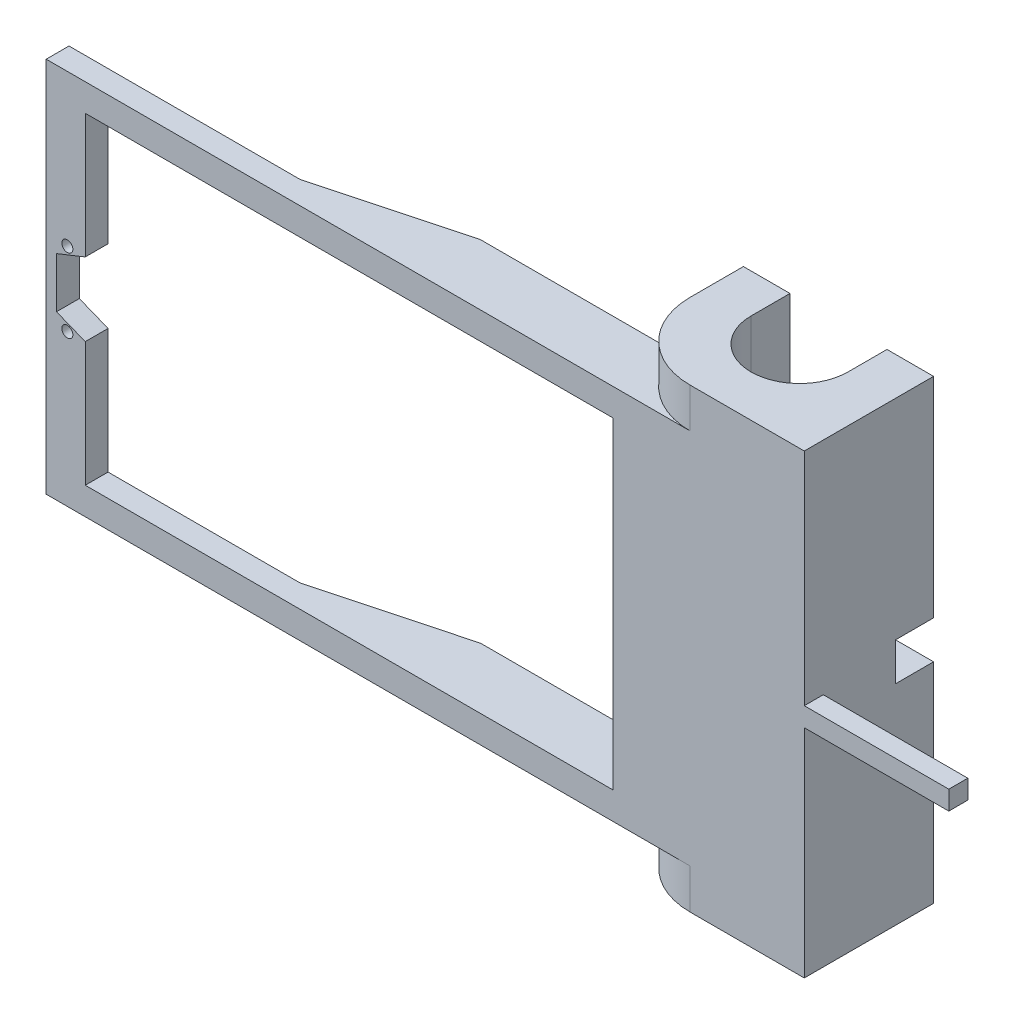
SolidWorks part; units mm, degrees
ref_plane "Front Plane" through (0, 0, 0) normal (0, 0, 1) x (1, 0, 0)
ref_plane "Top Plane" through (0, 0, 0) normal (0, 1, 0) x (1, 0, 0)
ref_plane "Right Plane" through (0, 0, 0) normal (1, 0, 0) x (0, 0, -1)
sketch "Sketch1" plane through (0, 0, 0) normal (0, 1, 0) x (1, 0, 0)
  line L1 (0, 0) -> (50, 0)
  line L2 (0, 0) -> (0, 34)
  line L3 (0, 34) -> (50, 34)
  line L4 (50, 0) -> (50, 34)
  dimension "D1" = 50
  dimension "D2" = 34
extrude "Boss-Extrude1" add sketch "Sketch1" along normal blind 120
sketch "Sketch2" plane through (0, 120, 0) normal (0, 1, 0) x (1, 0, 0)
  line L0 (0, 11) -> (50, 11) construction
  line L1 (0, 34) -> (0, 0) construction
  line L2 (50, 0) -> (50, 34) construction
  line L3 (25, 34) -> (25, 0) construction
  line L4 (50, 34) -> (0, 34) construction
  line L5 (0, 0) -> (50, 0) construction
  line L6 (12.25, 23.75) -> (12.25, 34)
  line L7 (12.25, 34) -> (37.75, 34)
  line L8 (37.75, 34) -> (37.75, 23.75)
  arc A0 (12.25, 23.75) -> (37.75, 23.75) centre (25, 23.75) ccw
  dimension "D1" = 23
extrude "Cut-Extrude2" cut sketch "Sketch2" against normal blind 120
fillet "Fillet1" radius 20 2 edges at (50, 60, 0) (0, 60, 0)
sketch "Sketch3" plane through (0, 0, -34) normal (0, 0, -1) x (-1, 0, 0)
  line L0 (0, 120) -> (0, 0) construction
  line L1 (0, 102) -> (-9.75, 102)
  line L2 (0, 102) -> (0, 18)
  line L3 (0, 18) -> (-9.75, 18)
  line L4 (-9.75, 102) -> (-9.75, 18)
  line L5 (-12.25, 120) -> (0, 120) construction
  line L6 (-12.25, 0) -> (-12.25, 120) construction
  line L7 (-12.25, 0) -> (0, 0) construction
  dimension "D1" = 18
  dimension "D2" = 2.5
  dimension "D3" = 18
extrude "Cut-Extrude3" cut sketch "Sketch3" against normal blind 31
sketch "Sketch4" plane through (0, 0, -34) normal (0, 0, -1) x (-1, 0, 0)
  line L0 (-37.75, 0) -> (-37.75, 120) construction
  line L1 (-37.75, 65) -> (-50, 65)
  line L2 (-37.75, 65) -> (-37.75, 55)
  line L3 (-37.75, 55) -> (-50, 55)
  line L4 (-50, 65) -> (-50, 55)
  line L5 (-50, 120) -> (-50, 0) construction
  line L6 (-50, 0) -> (-37.75, 0) construction
  dimension "D1" = 10
  dimension "D2" = 55
extrude "Cut-Extrude4" cut sketch "Sketch4" against normal blind 10
sketch "Sketch7" plane through (50, 0, 0) normal (1, 0, 0) x (0, 0, -1)
  line L0 (0, 0) -> (0, 120) construction
  line L1 (0, 62) -> (5, 62)
  line L2 (0, 62) -> (0, 57)
  line L3 (0, 57) -> (5, 57)
  line L4 (5, 62) -> (5, 57)
  line L5 (0, 0) -> (20, 0) construction
  point P6 (2.5, 57)
  dimension "D1" = 5
  dimension "D2" = 5
  dimension "D3" = 57
extrude "Boss-Extrude2" add sketch "Sketch7" along normal blind 38 and the other way blind 23
sketch "Sketch8" plane through (9.75, 0, 0) normal (-1, 0, 0) x (0, 0, 1)
  line L0 (0, 120) -> (0, 0) construction
  line L1 (-3, 102) -> (0, 102)
  line L2 (-3, 102) -> (-3, 18)
  line L3 (-3, 18) -> (0, 18)
  line L4 (0, 102) -> (0, 18)
extrude "Boss-Extrude3" add sketch "Sketch8" along normal blind 10 and the other way blind 10
fillet "Fillet3" radius 5 1 edges at (9.75, 60, -3)
sketch "Sketch9" plane through (-0.25, 0, 0) normal (-1, 0, 0) x (0, 0, 1)
  line L0 (-3, 102) -> (-3, 18) construction
  line L1 (-3, 76) -> (0, 76)
  line L2 (-3, 76) -> (-3, 70)
  line L3 (-3, 70) -> (0, 70)
  line L4 (0, 76) -> (0, 70)
  line L5 (0, 18) -> (0, 102) construction
  line L6 (-0.0016, 102) -> (-4.0957, 102) construction
  line L7 (-3, 50) -> (0, 50)
  line L8 (-3, 50) -> (-3, 44)
  line L9 (-3, 44) -> (0, 44)
  line L10 (0, 50) -> (0, 44)
  line L11 (-3, 18) -> (0, 18) construction
  dimension "D1" = 6
  dimension "D2" = 6
  dimension "D3" = 26
  dimension "D4" = 26
extrude "Boss-Extrude4" add sketch "Sketch9" along normal blind 146
sketch "Sketch10" plane through (-146.25, 0, 0) normal (-1, 0, 0) x (0, 0, 1)
  line L1 (-3, 76) -> (0, 76)
  line L2 (-3, 76) -> (-3, 44)
  line L3 (-3, 44) -> (0, 44)
  line L4 (0, 76) -> (0, 44)
extrude "Boss-Extrude5" add sketch "Sketch10" along normal blind 6
fillet "Fillet4" 2 edges at (-152.25, 76, -1.5) (-152.25, 44, -1.5) type full round first side face at (-76.25, 76, -1.5) second side face at (-76.25, 44, -1.5) middle face at (-152.25, 60, -1.5)
sketch "Sketch12" plane through (0, 0, -3) normal (0, 0, -1) x (-1, 0, 0)
  line L1 (146.25, 70) -> (138.25, 70)
  line L2 (146.25, 70) -> (146.25, 67.5)
  line L3 (146.25, 67.5) -> (138.25, 67.5)
  line L4 (138.25, 70) -> (138.25, 67.5)
  line L5 (146.25, 50) -> (138.25, 50)
  line L6 (146.25, 50) -> (146.25, 52.5)
  line L7 (146.25, 52.5) -> (138.25, 52.5)
  line L8 (138.25, 50) -> (138.25, 52.5)
  dimension "D1" = 2.5
  dimension "D2" = 2.5
  dimension "D3" = 8
  dimension "D4" = 8
extrude "Boss-Extrude6" add sketch "Sketch12" against normal up to vertex (3 mm away) up to point (-136.25, 44, 0)
fillet "Fillet5" radius 2 4 edges at (-146.25, 67.5, -1.5) (-146.25, 52.5, -1.5) (-138.25, 52.5, -1.5) (-138.25, 67.5, -1.5)
sketch "Sketch13" plane through (0, 0, -3) normal (0, 0, -1) x (-1, 0, 0)
  line L0 (132.4597, 76) -> (132.4597, 44) construction
  line L1 (136.25, 76) -> (0.25, 76) construction
  line L2 (136.25, 44) -> (0.25, 44) construction
  line L3 (142.25, 67.5) -> (142.25, 52.5) construction
  line L4 (140.25, 67.5) -> (144.25, 67.5) construction
  line L5 (144.25, 52.5) -> (140.25, 52.5) construction
  circle A0 centre (143.75, 69.25) radius 1.25
  circle A1 centre (143.75, 50.75) radius 1.25
  dimension "D3" = 1.75
  dimension "D5" = 2.5
  dimension "D6" = 2.5
  dimension "D1" = 32
  dimension "D2" = 15
  dimension "D4" = 1.75
  dimension "D7" = 5.5
  dimension "D8" = 5.5
extrude "Cut-Extrude5" cut sketch "Sketch13" against normal up to vertex (3 mm away) up to point (-136.25, 76, 0)
sketch "Sketch14" plane through (0, 0, -3) normal (0, 0, -1) x (-1, 0, 0)
  line L0 (138.25, 70) -> (0.25, 70) construction
  line L1 (13.25, 70) -> (18.25, 70)
  line L2 (13.25, 70) -> (13.25, 50)
  line L3 (13.25, 50) -> (18.25, 50)
  line L4 (18.25, 70) -> (18.25, 50)
  line L5 (138.25, 50) -> (0.25, 50) construction
  line L6 (0.25, 70) -> (0.25, 50) construction
  line L7 (31.25, 70) -> (36.25, 70)
  line L8 (31.25, 70) -> (31.25, 50)
  line L9 (31.25, 50) -> (36.25, 50)
  line L10 (36.25, 70) -> (36.25, 50)
  line L11 (49.25, 70) -> (54.25, 70)
  line L12 (49.25, 70) -> (49.25, 50)
  line L13 (49.25, 50) -> (54.25, 50)
  line L14 (54.25, 70) -> (54.25, 50)
  line L15 (67.25, 70) -> (72.25, 70)
  line L16 (67.25, 70) -> (67.25, 50)
  line L17 (67.25, 50) -> (72.25, 50)
  line L18 (72.25, 70) -> (72.25, 50)
  line L19 (85.25, 70) -> (90.25, 70)
  line L20 (85.25, 70) -> (85.25, 50)
  line L21 (85.25, 50) -> (90.25, 50)
  line L22 (90.25, 70) -> (90.25, 50)
  line L23 (103.25, 70) -> (108.25, 70)
  line L24 (103.25, 70) -> (103.25, 50)
  line L25 (103.25, 50) -> (108.25, 50)
  line L26 (108.25, 70) -> (108.25, 50)
  line L27 (121.25, 70) -> (126.25, 70)
  line L28 (121.25, 70) -> (121.25, 50)
  line L29 (121.25, 50) -> (126.25, 50)
  line L30 (126.25, 70) -> (126.25, 50)
  dimension "D1" = 13
  dimension "D2" = 5
  dimension "D3" = 5
  dimension "D4" = 13
  dimension "D5" = 5
  dimension "D6" = 13
  dimension "D7" = 5
  dimension "D8" = 13
  dimension "D9" = 5
  dimension "D10" = 13
  dimension "D11" = 5
  dimension "D12" = 13
  dimension "D13" = 5
  dimension "D14" = 23
extrude "Boss-Extrude7" add sketch "Sketch14" against normal up to surface (3 mm away) up to face at (-145, 69.25, 0)
sketch "Sketch15" plane through (0, 0, -3) normal (0, 0, -1) x (-1, 0, 0)
  circle A3 centre (143.75, 69.25) radius 1.55
  circle A4 centre (143.75, 69.25) radius 1.55
  circle A6 centre (143.75, 50.75) radius 1.55
  circle A7 centre (143.75, 50.75) radius 1.55
  dimension "D1" = 0.3
  dimension "D2" = 0.3
extrude "Cut-Extrude7" cut sketch "Sketch15" against normal blind 10
sketch "Sketch16" plane through (0, 0, -3) normal (0, 0, -1) x (-1, 0, 0)
  line L0 (-9.75, 18) -> (-9.75, 102) construction
  line L1 (-9.75, 76) -> (136.25, 76)
  line L2 (-9.75, 76) -> (-9.75, 73.8)
  line L3 (-9.75, 73.8) -> (136.25, 73.8)
  line L4 (136.25, 76) -> (136.25, 73.8)
  line L6 (-9.75, 102) -> (-9.75, 18) construction
  line L7 (-9.75, 46.2) -> (136.25, 46.2)
  line L8 (-9.75, 46.2) -> (-9.75, 44)
  line L9 (-9.75, 44) -> (136.25, 44)
  line L10 (136.25, 46.2) -> (136.25, 44)
  arc A0 (136.25, 44) -> (136.25, 76) centre (136.25, 60) ccw construction
  dimension "D1" = 146
  dimension "D2" = 2.2
  dimension "D3" = 146
  dimension "D4" = 2.2
extrude "Boss-Extrude10" add sketch "Sketch16" along normal blind 2
sketch "Sketch17" plane through (0, 0, -3) normal (0, 0, -1) x (-1, 0, 0)
  line L0 (140.25, 67.5) -> (144.25, 67.5) construction
  line L1 (141.0019, 67.5) -> (147.1292, 67.5)
  line L2 (138.25, 67.5) -> (138.25, 66.5)
  line L3 (138.25, 66.5) -> (147.1292, 66.5)
  line L4 (147.1292, 67.5) -> (147.1292, 66.5)
  line L5 (126.25, 60) -> (147.1292, 60) construction
  line L6 (138.25, 70) -> (141.0019, 70)
  line L7 (138.25, 70) -> (138.25, 67.5)
  line L9 (141.0019, 70) -> (141.0019, 67.5)
  line L10 (126.25, 50) -> (126.25, 70) construction
  line L11 (141.0019, 50) -> (141.0019, 52.5)
  line L12 (138.25, 50) -> (138.25, 52.5)
  line L13 (138.25, 50) -> (141.0019, 50)
  line L14 (147.1292, 52.5) -> (147.1292, 53.5)
  line L15 (138.25, 53.5) -> (147.1292, 53.5)
  line L16 (138.25, 52.5) -> (138.25, 53.5)
  line L17 (141.0019, 52.5) -> (147.1292, 52.5)
  dimension "D1" = 1
  dimension "D2" = 0
extrude "Boss-Extrude11" add sketch "Sketch17" against normal up to surface (3 mm away) up to face at (-142.2, 50.75, 0)
fillet "Fillet6" radius 5 1 edges at (-145.9821, 66.5, -1.5)
fillet "Fillet7" radius 5 2 edges at (-138.25, 66.5, -1.5) (-145.9821, 53.5, -1.5)
fillet "Fillet8" radius 5 1 edges at (-138.25, 53.5, -1.5)
sketch "Sketch19" plane through (0, 0, -34) normal (0, 0, -1) x (-1, 0, 0)
  line L0 (-50, 120) -> (0, 120) construction
  line L1 (0, 120) -> (0, 0) construction
sketch "Sketch21" plane through (0, 0, -34) normal (0, 0, -1) x (-1, 0, 0)
  line L0 (-50, 120) -> (0, 120) construction
  line L1 (-50, 120) -> (-50, 65) construction
  line L2 (0, 120) -> (0, 0) construction
  line L3 (-50, 0) -> (-37.75, 0) construction
  line L4 (-50, 55) -> (-50, 0) construction
  circle A0 centre (-44, 114) radius 1.4
  circle A1 centre (-6, 114) radius 1.4
  circle A2 centre (-44, 6) radius 1.4
  circle A3 centre (-6, 6) radius 1.4
  dimension "D1" = 6
  dimension "D3" = 6
  dimension "D4" = 6
  dimension "D2" = 6
  dimension "D5" = 6
extrude "Cut-Extrude8" cut sketch "Sketch21" against normal blind 20
sketch "Sketch22" plane through (0, 0, 0) normal (0, 0, 1) x (1, 0, 0)
  line L0 (-143.75, 69.25) -> (-143.75, 40.9227) construction
  line L1 (-143.75, 69.25) -> (-143.75, 79.381) construction
  line L2 (-143.75, 69.25) -> (-158.7698, 69.25) construction
  line L3 (-143.75, 50.75) -> (-164.5265, 50.75) construction
  line L5 (-146.1962, 71.4735) -> (-141.5912, 71.4735)
  line L6 (-146.1962, 71.4735) -> (-146.1962, 67.0856)
  line L7 (-146.1962, 67.0856) -> (-141.5912, 67.0856)
  line L8 (-141.5912, 71.4735) -> (-141.5912, 67.0856)
extrude "Boss-Extrude12" add sketch "Sketch22" against normal up to vertex (3 mm away) up to point (-136.25, 76, -3)
sketch "Sketch24" plane through (0, 0, 0) normal (0, 0, 1) x (1, 0, 0)
  line L0 (-143.75, 50.75) -> (-143.75, 81.4495) construction
  circle A1 centre (-143.75, 70.3717) radius 1.45
extrude "Cut-Extrude9" cut sketch "Sketch24" against normal blind 10 contours A1
sketch "Sketch26" plane through (0, 0, 0) normal (0, 0, 1) x (1, 0, 0)
  line L1 (-146.7469, 52.5653) -> (-140.9319, 52.5653)
  line L2 (-146.7469, 52.5653) -> (-146.7469, 48.6779)
  line L3 (-146.7469, 48.6779) -> (-140.9319, 48.6779)
  line L4 (-140.9319, 52.5653) -> (-140.9319, 48.6779)
extrude "Boss-Extrude13" add sketch "Sketch26" against normal up to vertex (3 mm away) up to point (-136.25, 76, -3)
sketch "Sketch27" plane through (0, 0, 0) normal (0, 0, 1) x (1, 0, 0)
  line L0 (-143.75, 70.3717) -> (-143.75, 42.5469) construction
  circle A0 centre (-143.75, 50.0683) radius 1.45
extrude "Cut-Extrude10" cut sketch "Sketch27" against normal blind 10
sketch "Sketch28" plane through (0, 0, 0) normal (0, 0, 1) x (1, 0, 0)
  line L1 (-126.25, 70) -> (-121.25, 70)
  line L2 (-126.25, 70) -> (-126.25, 50)
  line L3 (-126.25, 50) -> (-121.25, 50)
  line L4 (-121.25, 70) -> (-121.25, 50)
extrude "Cut-Extrude12" cut sketch "Sketch28" against normal blind 10
sketch "Sketch29" plane through (0, 0, -3) normal (0, 0, -1) x (-1, 0, 0)
  line L1 (108.25, 70) -> (0.25, 70)
  line L2 (108.25, 70) -> (108.25, 50)
  line L3 (108.25, 50) -> (0.25, 50)
  line L4 (0.25, 70) -> (0.25, 50)
extrude "Boss-Extrude14" add sketch "Sketch29" against normal up to vertex (3 mm away) up to point (-136.25, 44, 0)
sketch "Sketch30" plane through (0, 0, -3) normal (0, 0, -1) x (-1, 0, 0)
  line L0 (-4.75, 60) -> (35.5343, 60) construction
  line L1 (-4.75, 73.8) -> (-4.75, 46.2) construction
  line L2 (0, 120) -> (0, 0) construction
  line L3 (4.75, 32.4863) -> (-4.75, 32.4863)
  line L4 (4.75, 32.4863) -> (4.75, 87.5137)
  line L5 (4.75, 87.5137) -> (-4.75, 87.5137)
  line L6 (-4.75, 32.4863) -> (-4.75, 87.5137)
  line L7 (4.75, 32.4863) -> (-4.75, 87.5137) construction
  line L8 (4.75, 87.5137) -> (-4.75, 32.4863) construction
  line L9 (-4.75, 102) -> (-4.75, 76) construction
  point P4 (0, 60)
extrude "Boss-Extrude15" add sketch "Sketch30" against normal up to vertex (3 mm away) up to point (-136.25, 44, 0)
sketch "Sketch32" plane through (0, 0, -3) normal (0, 0, -1) x (-1, 0, 0)
  circle A0 centre (136.0726, 60.03) radius 16
  circle A1 centre (136.0726, 60.03) radius 10.1774
extrude "Boss-Extrude17" add sketch "Sketch32" along normal blind 3
sketch "Sketch33" plane through (0, 0, -3) normal (0, 0, -1) x (-1, 0, 0)
  line L0 (125.8952, 60.03) -> (146.25, 60.03) construction
  line L1 (136.0726, 70) -> (136.0726, 49.8526) construction
  line L2 (138.1168, 70) -> (134.0284, 70) construction
  line L4 (108.25, 50) -> (136.0726, 50)
  line L5 (108.25, 50) -> (108.25, 70)
  line L6 (108.25, 70) -> (136.0726, 70)
  line L7 (136.0726, 50) -> (136.0726, 70)
  circle A0 centre (136.0726, 60.03) radius 10.1774 construction
  arc A1 (134.3468, 50) -> (137.7984, 50) centre (136.0726, 60.03) ccw construction
extrude "Cut-Extrude13" cut sketch "Sketch33" along normal blind 43
sketch "Sketch34" plane through (0, 0, -3) normal (0, 0, -1) x (-1, 0, 0)
  line L1 (-4.75, 76) -> (136.0726, 76)
  line L2 (-4.75, 76) -> (-4.75, 44.03)
  line L3 (-4.75, 44.03) -> (136.0726, 44.03)
  line L4 (136.0726, 76) -> (136.0726, 44.03)
  arc A0 (123.6067, 50) -> (123.5586, 70) centre (136.0726, 60.03) ccw construction
extrude "Boss-Extrude18" add sketch "Sketch34" along normal blind 3
sketch "Sketch35" plane through (0, 0, -3) normal (0, 0, 1) x (1, 0, 0)
  line L1 (-136.0726, 70) -> (-108.25, 70)
  line L2 (-136.0726, 70) -> (-136.0726, 50)
  line L3 (-136.0726, 50) -> (-108.25, 50)
  line L4 (-108.25, 70) -> (-108.25, 50)
extrude "Cut-Extrude14" cut sketch "Sketch35" against normal blind 3
sketch "Sketch36" plane through (0, 0, -3) normal (0, 0, -1) x (-1, 0, 0)
  line L0 (-4.75, 73.8) -> (-4.75, 46.2) construction
  line L1 (-8.8645, 78.7942) -> (-0.6355, 78.7942)
  line L2 (-8.8645, 78.7942) -> (-8.8645, 41.2058)
  line L3 (-8.8645, 41.2058) -> (-0.6355, 41.2058)
  line L4 (-0.6355, 78.7942) -> (-0.6355, 41.2058)
  line L5 (-8.8645, 78.7942) -> (-0.6355, 41.2058) construction
  line L6 (-8.8645, 41.2058) -> (-0.6355, 78.7942) construction
  point P0 (-4.75, 60)
extrude "Boss-Extrude19" add sketch "Sketch36" along normal blind 3
sketch "Sketch38" plane through (0, 0, -3) normal (0, 0, 1) x (1, 0, 0)
  line L0 (-143.75, 68.9217) -> (-143.75, 71.8217) construction
  line L1 (-143.75, 71.8217) -> (-145.2, 70.3717) construction
  line L2 (-145.2, 70.3717) -> (-142.3, 70.3717) construction
  line L3 (-142.3, 70.3717) -> (-143.75, 71.8217) construction
  circle A0 centre (-143.75, 70.3717) radius 1.45 construction
  circle A1 centre (-143.75, 70.3717) radius 1.45 construction
  circle A2 centre (-143.75, 70.3717) radius 1.45
extrude "Cut-Extrude15" cut sketch "Sketch38" against normal blind 3
sketch "Sketch39" plane through (0, 0, 0) normal (0, 0, 1) x (1, 0, 0)
  circle A0 centre (-143.75, 50.0683) radius 1.45
extrude "Cut-Extrude16" cut sketch "Sketch39" against normal blind 23
sketch "Sketch43" plane through (-50.253, -9.9664, 0) normal (0, 0, 1) x (1, 0, 0)
  line L1 (-119.0077, 13.5846) -> (-19.9477, 13.5846)
  line L2 (-119.0077, 13.5846) -> (-119.0077, 3.6653)
  line L3 (-119.0077, 3.6653) -> (-19.9477, 3.6653)
  line L4 (-19.9477, 13.5846) -> (-19.9477, 3.6653)
extrude "Boss-Extrude21" add sketch "Sketch43" along normal blind 10 separate body
sketch "Sketch44" plane through (0, 0, 10) normal (0, 0, 1) x (1, 0, 0)
  line L3 (-59.0621, -19.9166) -> (-176.5979, -19.9166)
  line L4 (-59.0621, -19.9166) -> (-59.0621, 13.2072)
  line L5 (-59.0621, 13.2072) -> (-176.5979, 13.2072)
  line L6 (-176.5979, -19.9166) -> (-176.5979, 13.2072)
  line L7 (-59.0621, -19.9166) -> (-176.5979, 13.2072) construction
  line L8 (-59.0621, 13.2072) -> (-176.5979, -19.9166) construction
  point P0 (-117.83, -3.3547)
  point P18 (-152.25, 63.9879)
  point P222 (-111.4924, -6.5024)
  point P516 (-146.1675, 63.9879)
sketch "Sketch46" plane through (0, 0, 0) normal (0, 0, -1) x (-1, 0, 0)
  line L1 (70.2007, 3.6182) -> (169.2607, 3.6182)
  line L2 (70.2007, 3.6182) -> (70.2007, -6.301)
  line L3 (70.2007, -6.301) -> (169.2607, -6.301)
  line L4 (169.2607, 3.6182) -> (169.2607, -6.301)
  line L5 (119.7307, -6.301) -> (119.7307, 3.6182) construction
  line L6 (70.2007, -1.3414) -> (169.2607, -1.3414) construction
  point P244 (119.7307, -1.3414)
extrude "Cut-Extrude18" cut sketch "Sketch46" against normal up to vertex rebuild error yes up to point (-46.2931, 9.3782, 10)
extrude "Cut-Extrude19" cut sketch "Sketch44" against normal blind 60
sketch "Sketch47" plane through (0, 0, -6) normal (0, 0, -1) x (-1, 0, 0)
  line L0 (152.0726, 60.03) -> (108.25, 60) construction
  line L1 (108.25, 50) -> (108.25, 70) construction
  line L2 (149.3194, 60.0281) -> (149.3194, 109.5581)
  line L3 (149.3194, 60.0281) -> (149.3194, 10.4981)
  line L4 (139.048, 60.0211) -> (139.048, 109.5511)
  line L5 (139.048, 60.0211) -> (139.048, 10.4911)
  line L6 (139.048, 109.5511) -> (149.3194, 109.5581)
  line L7 (139.048, 10.4911) -> (149.3194, 10.4981)
  arc A0 (136.0726, 44.03) -> (135.093, 76) centre (136.0726, 60.03) ccw construction
  arc A1 (136.25, 44.031) -> (138.8303, 75.7906) centre (136.0726, 60.03) ccw construction
extrude "Boss-Extrude24" add sketch "Sketch47" against normal blind 4
sketch "Sketch48" plane through (0, 0, 0) normal (0, 0, 1) x (1, 0, 0)
  circle A0 centre (-143.7464, 50.0903) radius 1.4724
extrude "Cut-Extrude20" cut sketch "Sketch48" against normal blind 13
sketch "Sketch49" plane through (0, 0, 0) normal (0, 0, 1) x (1, 0, 0)
  circle A0 centre (-144.4569, 71.6357) radius 0.0018
  circle A1 centre (-143.7629, 70.3908) radius 1.4731
extrude "Cut-Extrude22" cut sketch "Sketch49" against normal blind 13
sketch "Sketch50" plane through (0, 0, -2) normal (0, 0, 1) x (1, 0, 0)
  line L0 (-149.3194, 10.4981) -> (-149.3194, 51.0566) construction
  line L1 (-149.3194, 39.0131) -> (-156.9556, 39.0131)
  line L2 (-149.3194, 39.0131) -> (-149.3194, 82.5417)
  line L3 (-149.3194, 82.5417) -> (-156.9556, 82.5417)
  line L4 (-156.9556, 39.0131) -> (-156.9556, 82.5417)
  line L5 (-153.1375, 82.5417) -> (-153.1375, 39.0131) construction
  line L6 (-149.3194, 60.7774) -> (-156.9556, 60.7774) construction
  point P188 (-153.1375, 60.7774)
extrude "Cut-Extrude24" cut sketch "Sketch50" along normal blind 13
sketch "Sketch52" plane through (0, 0, -6) normal (0, 0, -1) x (-1, 0, 0)
  line L0 (149.3194, 69.0035) -> (149.3194, 109.5581) construction
  line L1 (149.3194, 81.2044) -> (164.0913, 81.2044)
  line L2 (149.3194, 81.2044) -> (149.3194, 35.3031)
  line L3 (149.3194, 35.3031) -> (164.0913, 35.3031)
  line L4 (164.0913, 81.2044) -> (164.0913, 35.3031)
  line L5 (156.7053, 35.3031) -> (156.7053, 81.2044) construction
  line L6 (149.3194, 58.2538) -> (164.0913, 58.2538) construction
  point P180 (156.7053, 58.2538)
extrude "Cut-Extrude25" cut sketch "Sketch52" against normal blind 13
sketch "Sketch53" plane through (0, 0, -6) normal (0, 0, -1) x (-1, 0, 0)
  line L0 (139.048, 109.5511) -> (139.048, 75.7509) construction
  line L1 (139.048, 91.2748) -> (122.3222, 91.2748)
  line L2 (139.048, 91.2748) -> (139.048, 34.8794)
  line L3 (139.048, 34.8794) -> (122.3222, 34.8794)
  line L4 (122.3222, 91.2748) -> (122.3222, 34.8794)
  line L5 (130.6851, 34.8794) -> (130.6851, 91.2748) construction
  line L6 (139.048, 63.0771) -> (122.3222, 63.0771) construction
  point P284 (130.6851, 63.0771)
extrude "Cut-Extrude26" cut sketch "Sketch53" against normal blind 13
sketch "Sketch54" plane through (0, 0, -2) normal (0, 0, 1) x (1, 0, 0)
  line L1 (-149.3194, 109.5581) -> (-139.048, 109.5581)
  line L2 (-149.3194, 109.5581) -> (-149.3194, 10.4911)
  line L3 (-149.3194, 10.4911) -> (-139.048, 10.4911)
  line L4 (-139.048, 109.5581) -> (-139.048, 10.4911)
  line L5 (-144.1837, 10.4911) -> (-144.1837, 109.5581) construction
  line L6 (-149.3194, 60.0246) -> (-139.048, 60.0246) construction
  point P880 (-144.1837, 60.0246)
extrude "Cut-Extrude27" cut sketch "Sketch54" along normal blind 2 contours L2 L1 L4 L3
sketch "Sketch55" plane through (0, 0, -6) normal (0, 0, -1) x (-1, 0, 0)
  line L0 (149.3194, 60.0281) -> (108.25, 60) construction
  line L1 (149.3194, 10.4981) -> (149.3194, 109.5581) construction
  line L2 (108.25, 50) -> (108.25, 70) construction
  line L3 (139.048, 60.0211) -> (144.4728, 60.0248)
  line L4 (139.048, 109.5511) -> (139.048, 10.4911) construction
  line L5 (146.2609, 60.026) -> (146.2609, 66.026)
  line L6 (146.2609, 60.026) -> (146.2609, 54.026)
  line L7 (142.2899, 70.3908) -> (136.8332, 70.3908) construction
  line L8 (142.274, 50.0903) -> (137.2667, 50.0903) construction
  line L9 (146.2609, 66.026) -> (139.048, 70.3908)
  line L10 (144.4728, 49.6588) -> (144.4728, 70.3908)
  line L11 (144.4728, 49.6588) -> (137.0044, 49.6588) construction
  line L12 (142.2899, 70.3908) -> (144.4728, 70.3908) construction
  line L13 (143.7629, 71.8638) -> (143.7629, 30.3798) construction
  line L15 (140.3203, 52.216) -> (146.0026, 52.216)
  line L16 (140.3203, 52.216) -> (140.3203, 47.9647)
  line L17 (140.3203, 47.9647) -> (146.0026, 47.9647)
  line L18 (146.0026, 52.216) -> (146.0026, 47.9647)
  line L19 (140.3203, 52.216) -> (146.0026, 47.9647) construction
  line L20 (140.3203, 47.9647) -> (146.0026, 52.216) construction
  circle A0 centre (143.7629, 70.3908) radius 1.4731 construction
  circle A1 centre (143.7464, 50.0903) radius 1.4724 construction
  point P26 (144.4728, 60.0248)
  point P29 (143.1614, 50.0903)
extrude "Boss-Extrude27" add sketch "Sketch55" against normal blind 4 contours L16 L15 L18 L17
sketch "Sketch56" plane through (0, 0, -6) normal (0, 0, -1) x (-1, 0, 0)
  line L0 (108.25, 50) -> (108.25, 70) construction
  line L1 (149.3194, 60.0281) -> (108.25, 60) construction
  line L2 (149.3194, 10.4981) -> (149.3194, 109.5581) construction
  line L3 (143.7629, 70.3908) -> (143.7629, 40.2185) construction
  circle A0 centre (143.7629, 49.6579) radius 1.47
  point P12 (143.7629, 60.0243)
extrude "Cut-Extrude28" cut sketch "Sketch56" against normal blind 4
sketch "Sketch57" plane through (0, 0, -6) normal (0, 0, -1) x (-1, 0, 0)
  line L0 (149.3194, 60.0281) -> (108.25, 60) construction
  line L1 (149.3194, 10.4981) -> (149.3194, 109.5581) construction
  line L2 (108.25, 50) -> (108.25, 70) construction
  line L3 (139.048, 50.3848) -> (146.6063, 53.4025)
  line L4 (146.6063, 66.65) -> (146.6063, 53.4025) construction
  line L5 (139.048, 109.5511) -> (139.048, 10.4911) construction
  line L6 (143.7629, 70.3908) -> (139.048, 70.3908) construction
  line L7 (143.7629, 49.6579) -> (139.048, 49.6579) construction
  line L8 (139.048, 69.6573) -> (139.048, 50.3848)
  line L9 (146.6063, 53.4025) -> (146.6063, 66.65)
  line L10 (146.6063, 66.65) -> (139.048, 69.6573)
  point P9 (146.6063, 60.0263)
  point P21 (139.048, 60.0211)
extrude "Cut-Extrude29" cut sketch "Sketch57" against normal blind 4
sketch "Sketch58" plane through (0, 0, -2) normal (0, 0, 1) x (1, 0, 0)
  line L1 (-139.048, 109.5511) -> (23.1959, 109.5511)
  line L2 (-139.048, 109.5511) -> (-139.048, 102.7879)
  line L3 (-139.048, 102.7879) -> (23.1959, 102.7879)
  line L4 (23.1959, 109.5511) -> (23.1959, 102.7879)
  line L5 (-57.9261, 102.7879) -> (-57.9261, 109.5511) construction
  line L6 (-139.048, 106.1695) -> (23.1959, 106.1695) construction
  point P904 (-57.9261, 106.1695)
extrude "Boss-Extrude33" add sketch "Sketch58" against normal blind 4
sketch "Sketch59" plane through (0, 0, -2) normal (0, 0, 1) x (1, 0, 0)
  line L0 (-149.3194, 10.4981) -> (-139.048, 10.4911)
  line L1 (-139.048, 10.4911) -> (-139.048, 50.3848)
  line L2 (-139.048, 50.3848) -> (-146.6063, 53.4025)
  line L3 (-146.6063, 53.4025) -> (-146.6063, 66.65)
  line L4 (-146.6063, 66.65) -> (-139.048, 69.6573)
  line L5 (-139.048, 69.6573) -> (-139.048, 102.7879)
  line L6 (-139.048, 102.7879) -> (11.2822, 102.7879)
  line L7 (11.2822, 102.7879) -> (11.2822, 109.5511)
  line L8 (11.2822, 109.5511) -> (-149.3194, 109.5581)
  line L9 (-149.3194, 109.5581) -> (-149.3194, 10.4981)
extrude "Boss-Extrude38" add sketch "Sketch59" along normal blind 2 contours L9 L0 L1 L2 L3 L4 L5 L6 L7 L8
sketch "Sketch60" plane through (0, 0, -6) normal (0, 0, -1) x (-1, 0, 0)
  line L1 (149.3194, 109.5581) -> (-23.3262, 109.5581)
  line L2 (149.3194, 109.5581) -> (149.3194, 102.3831)
  line L3 (149.3194, 102.3831) -> (-23.3262, 102.3831)
  line L4 (-23.3262, 109.5581) -> (-23.3262, 102.3831)
  line L5 (62.9966, 102.3831) -> (62.9966, 109.5581) construction
  line L6 (149.3194, 105.9706) -> (-23.3262, 105.9706) construction
  point P1288 (62.9966, 105.9706)
extrude "Boss-Extrude40" add sketch "Sketch60" against normal blind 6
sketch "Sketch62" plane through (0, 0, -6) normal (0, 0, -1) x (-1, 0, 0)
  line L0 (-20, 102.3831) -> (-20, 0) construction
  line L1 (149.3194, 10.4981) -> (-20, 10.4981)
  line L2 (149.3194, 10.4981) -> (149.3194, 17.6774)
  line L3 (149.3194, 17.6774) -> (-20, 17.6774)
  line L4 (-20, 10.4981) -> (-20, 17.6774)
  line L5 (64.6597, 17.6774) -> (64.6597, 10.4981) construction
  line L6 (149.3194, 14.0878) -> (-20, 14.0878) construction
  point P644 (64.6597, 14.0878)
extrude "Boss-Extrude41" add sketch "Sketch62" against normal blind 6 contours L2 L1 L4 L3
sketch "Sketch63" plane through (0, 0, 0) normal (0, 0, 1) x (1, 0, 0)
  line L1 (-0.25, 102) -> (-132.8928, 102)
  line L2 (-0.25, 102) -> (-0.25, 22.4445)
  line L3 (-0.25, 22.4445) -> (-132.8928, 22.4445)
  line L4 (-132.8928, 102) -> (-132.8928, 22.4445)
  line L5 (-66.5714, 22.4445) -> (-66.5714, 102) construction
  line L6 (-0.25, 62.2222) -> (-132.8928, 62.2222) construction
  point P753 (-66.5714, 62.2222)
extrude "Cut-Extrude30" cut sketch "Sketch63" against normal blind 10
sketch "Sketch64" plane through (0, 0, -3) normal (0, 0, -1) x (-1, 0, 0)
  line L0 (-0.6355, 78.7942) -> (-4.75, 78.7942) construction
  line L1 (-3.0374, 78.7942) -> (0.25, 78.7942)
  line L2 (-3.0374, 78.7942) -> (-3.0374, 41.2058)
  line L3 (-3.0374, 41.2058) -> (0.25, 41.2058)
  line L4 (0.25, 78.7942) -> (0.25, 41.2058)
  line L5 (-1.3937, 41.2058) -> (-1.3937, 78.7942) construction
  line L6 (-3.0374, 60) -> (0.25, 60) construction
  line L7 (0.25, 44) -> (0.25, 18) construction
  point P1308 (-1.3937, 60)
extrude "Boss-Extrude42" add sketch "Sketch64" along normal blind 3
sketch "Sketch65" plane through (0, 0, 0) normal (0, 0, 1) x (1, 0, 0)
  line L0 (-139.048, 17.6774) -> (20, 17.6774) construction
  line L1 (20, 102.3831) -> (-0.2391, 102.3831)
  line L2 (20, 102.3831) -> (20, 17.6774)
  line L3 (20, 17.6774) -> (-0.2391, 17.6774)
  line L4 (-0.2391, 102.3831) -> (-0.2391, 17.6774)
  line L5 (9.8805, 17.6774) -> (9.8805, 102.3831) construction
  line L6 (20, 60.0303) -> (-0.2391, 60.0303) construction
  point P944 (9.8805, 60.0303)
extrude "Boss-Extrude43" add sketch "Sketch65" against normal blind 3
sketch "Sketch66" plane through (0, 120, 0) normal (0, 1, 0) x (1, 0, 0)
  line L0 (30, 0) -> (88, 0) construction
  line L1 (25, 11) -> (44.3992, 11)
  line L2 (25, 11) -> (25, 0)
  line L3 (25, 0) -> (44.3992, 0)
  line L4 (44.3992, 11) -> (44.3992, 0)
  line L5 (34.6996, 0) -> (34.6996, 11) construction
  line L6 (25, 5.5) -> (44.3992, 5.5) construction
  arc A0 (12.25, 23.75) -> (37.75, 23.75) centre (25, 23.75) ccw construction
  point P940 (34.6996, 5.5)
extrude "Boss-Extrude45" add sketch "Sketch66" against normal up to vertex (120 mm away) contours L2 L1 L4 L3 up to point (12.25, 0, -23.75)
sketch "Sketch67" plane through (0, 120, 0) normal (0, 1, 0) x (1, 0, 0)
  line L0 (20, 0) -> (44.3992, 0) construction
  line L1 (50, 34) -> (41.2113, 34)
  line L2 (50, 34) -> (50, 0)
  line L3 (50, 0) -> (41.2113, 0)
  line L4 (41.2113, 34) -> (41.2113, 0)
  line L5 (45.6056, 0) -> (45.6056, 34) construction
  line L6 (50, 17) -> (41.2113, 17) construction
  point P356 (45.6056, 17)
extrude "Boss-Extrude46" add sketch "Sketch67" against normal up to vertex (120 mm away) up to point (44.3992, 0, -6.1197)
sketch "Sketch68" plane through (37.75, 55, -34) normal (-1, 0, 0) x (0, 0, 1)
  line L0 (10, 0) -> (0, 0) construction
  line L1 (0, 10) -> (10, 10)
  line L2 (0, 10) -> (0, 0)
  line L3 (0, 0) -> (10, 0)
  line L4 (10, 10) -> (10, 0)
  line L5 (5, 0) -> (5, 10) construction
  line L6 (0, 5) -> (10, 5) construction
  line L7 (10, 0) -> (10, 10) construction
  point P341 (5, 5)
extrude "Cut-Extrude31" cut sketch "Sketch68" against normal up to vertex (12.25 mm away) up to point (50, 120, -34)
sketch "Sketch69" plane through (0, 0, 0) normal (0, 0, 1) x (1, 0, 0)
  line L0 (-143.7629, 70.3908) -> (-143.7629, 76.5844) construction
  line L5 (76.3064, 14.5221) -> (76.3064, 106.0381) construction
  line L6 (50, 60.2801) -> (102.6128, 60.2801) construction
  line L7 (-143.7629, 49.6579) -> (-143.7629, 43.0785) construction
  circle A0 centre (-143.7629, 70.3908) radius 1.4731
  point P296 (76.3064, 60.2801)
extrude "Boss-Extrude49" add sketch "Sketch69" against normal up to vertex (6 mm away) up to point (-139.048, 69.6573, -6)
sketch "Sketch70" plane through (0, 0, -6) normal (0, 0, -1) x (-1, 0, 0)
  line L0 (143.7629, 49.6579) -> (143.7629, 72.3414) construction
  circle A0 centre (143.7629, 69.9091) radius 1.5722
extrude "Cut-Extrude32" cut sketch "Sketch70" against normal blind 10
sketch "Sketch71" plane through (0, 0, -2) normal (0, 0, -1) x (-1, 0, 0)
  circle A0 centre (143.7777, 49.6263) radius 1.6984
extrude "Boss-Extrude51" add sketch "Sketch71" along normal up to vertex (4 mm away) up to point (-149.3194, 109.5581, -6)
sketch "Sketch72" plane through (0, 0, -6) normal (0, 0, -1) x (-1, 0, 0)
  line L0 (143.7629, 69.9091) -> (143.7629, 33.6483) construction
  circle A0 centre (143.7629, 50.4048) radius 1.4
extrude "Cut-Extrude33" cut sketch "Sketch72" against normal blind 10 contours A0
sketch "Sketch73" plane through (0, 0, -14) normal (0, 0, -1) x (-1, 0, 0)
  line L0 (-6, 114) -> (-52.7949, 114) construction
  line L1 (-44.3808, 120) -> (-44.3808, 106.6712) construction
  line L2 (-50, 120) -> (0, 120) construction
  circle A0 centre (-44.3808, 114) radius 1.4
extrude "Cut-Extrude34" cut sketch "Sketch73" along normal up to vertex (20 mm away) up to point (50, 120, -34)
sketch "Sketch74" plane through (0, 0, -14) normal (0, 0, -1) x (-1, 0, 0)
  line L0 (-6, 6) -> (-54.1955, 6) construction
  line L1 (-44.2711, 0) -> (-43.875, 0) construction
  line L2 (-50, 0) -> (-37.75, 0) construction
  line L3 (-43.875, 0) -> (-43.875, 7.8729) construction
  circle A0 centre (-43.875, 6) radius 1.4
extrude "Cut-Extrude35" cut sketch "Sketch74" along normal up to vertex (20 mm away) up to point (50, 0, -34)
sketch "Sketch75" plane through (0, 0, 0) normal (0, 0, 1) x (1, 0, 0)
  circle A1 centre (-143.8207, 70.1551) radius 1.8249
extrude "Boss-Extrude52" add sketch "Sketch75" against normal up to vertex (6 mm away) up to point (-139.048, 69.6573, -6)
sketch "Sketch76" plane through (0, 0, -6) normal (0, 0, -1) x (-1, 0, 0)
  line L0 (143.7629, 50.4048) -> (143.7629, 75.4961) construction
  circle A0 centre (143.847, 50.2154) radius 1.6072
  circle A1 centre (143.7629, 69.7608) radius 1.45
extrude "Cut-Extrude36" cut sketch "Sketch76" against normal blind 10 contours A1
sketch "Sketch78" plane through (0, 0, -6) normal (0, 0, -1) x (-1, 0, 0)
  circle A0 centre (145.2566, 48.6956) radius 3.6954
extrude "Boss-Extrude55" add sketch "Sketch78" against normal up to vertex (6 mm away) contours A0 up to point (-149.3194, 109.5581, 0)
sketch "Sketch79" plane through (0, 0, -6) normal (0, 0, -1) x (-1, 0, 0)
  line L0 (143.7629, 69.7608) -> (143.7629, 47.9185) construction
  circle A0 centre (143.7629, 50.308) radius 1.45
extrude "Cut-Extrude37" cut sketch "Sketch79" against normal blind 10 contours A0
sketch "Sketch80" plane through (0, 0, -6) normal (0, 0, -1) x (-1, 0, 0)
  line L0 (149.3194, 109.5581) -> (-5.7171, 109.5581) construction
  line L1 (88.525, 109.5581) -> (-8.8504, 109.5581)
  line L2 (88.525, 109.5581) -> (88.525, 102.3884)
  line L3 (88.525, 102.3884) -> (-8.8504, 102.3884)
  line L4 (-8.8504, 109.5581) -> (-8.8504, 102.3884)
  line L5 (39.8373, 102.3884) -> (39.8373, 109.5581) construction
  line L6 (88.525, 105.9733) -> (-8.8504, 105.9733) construction
  point P1020 (39.8373, 105.9733)
extrude "Boss-Extrude56" add sketch "Sketch80" along normal blind 10
sketch "Sketch81" plane through (0, 0, -6) normal (0, 0, -1) x (-1, 0, 0)
  line L0 (88.525, 109.2281) -> (88.525, 10.4981) construction
  line L1 (88.525, 102.3884) -> (88.525, 109.5581) construction
  line L2 (139.048, 10.4981) -> (-5.7171, 10.4981) construction
  line L3 (139.048, 17.6774) -> (-5.7171, 17.6774) construction
  line L4 (88.525, 10.4981) -> (-5.7171, 10.4981)
  line L5 (88.525, 10.4981) -> (88.525, 17.6774)
  line L6 (88.525, 17.6774) -> (-5.7171, 17.6774)
  line L7 (-5.7171, 10.4981) -> (-5.7171, 17.6774)
  line L8 (41.4039, 17.6774) -> (41.4039, 10.4981) construction
  line L9 (88.525, 14.0878) -> (-5.7171, 14.0878) construction
  point P2358 (41.4039, 14.0878)
extrude "Boss-Extrude57" add sketch "Sketch81" along normal blind 10
sketch "Sketch82" plane through (0, 10.4981, 0) normal (0, -1, 0) x (-1, 0, 0)
  line L0 (88.525, 6) -> (88.525, 16)
  line L1 (88.525, 16) -> (51.1201, 16)
  line L2 (-0.4041, 16) -> (88.525, 16) construction
  line L3 (51.1201, 16) -> (88.525, 6)
extrude "Cut-Extrude38" cut sketch "Sketch82" against normal blind 134
